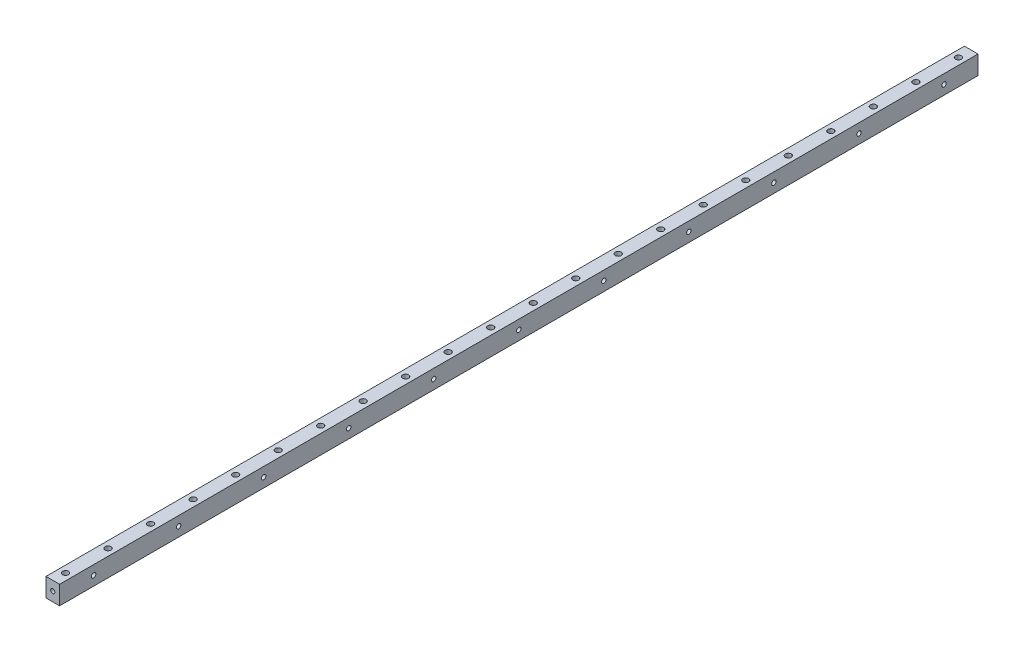
SolidWorks part; units mm, degrees
ref_plane "Front Plane" through (0, 0, 0) normal (0, 0, 1) x (1, 0, 0)
ref_plane "Top Plane" through (0, 0, 0) normal (0, 1, 0) x (1, 0, 0)
ref_plane "Right Plane" through (0, 0, 0) normal (1, 0, 0) x (0, 0, -1)
sketch "Sketch1" plane through (0, 0, 0) normal (0, 0, 1) x (1, 0, 0)
  line L1 (-4, -5.5) -> (4, -5.5)
  line L2 (-4, -5.5) -> (-4, 5.5)
  line L3 (-4, 5.5) -> (4, 5.5)
  line L4 (4, -5.5) -> (4, 5.5)
  line L5 (-4, -5.5) -> (4, 5.5) construction
  line L6 (-4, 5.5) -> (4, -5.5) construction
  point P0 (0, 0)
  dimension "D1" = 8
  dimension "D2" = 11
extrude "Boss-Extrude1" add sketch "Sketch1" along normal blind 540
sketch "Sketch2" plane through (0, 5.5, 0) normal (0, 1, 0) x (1, 0, 0)
  line L0 (4, 0) -> (-4, 0) construction
  circle A0 centre (0, -7.5) radius 1.75
  dimension "D2" = 3.5
  dimension "D1" = 7.5
extrude "Cut-Extrude1" cut sketch "Sketch2" against normal through all
pattern_linear "LPattern1" count 22 spacing 25 along (0, 0, 1) of "Cut-Extrude1"
sketch "Sketch3" plane through (-4, 0, 0) normal (-1, 0, 0) x (0, 0, 1)
  line L0 (0, 0) -> (540, 0) construction
  line L1 (540, 5.5) -> (540, -5.5) construction
  line L2 (0, 5.5) -> (0, -5.5) construction
  circle A0 centre (20, 0) radius 1.3
  dimension "D1" = 2.6
  dimension "D2" = 20
extrude "Cut-Extrude2" cut sketch "Sketch3" against normal through all
pattern_linear "LPattern2" count 11 spacing 50 along (0, 0, 1) of "Cut-Extrude2"
hole_wizard "M3 Tapped Hole1" positions "Sketch6" profile "Sketch8" tap size "M3" standard "ISO"
sketch "Sketch6" plane through (0, 0, 0) normal (0, 0, -1) x (-1, 0, 0)
  line L0 (-4, 5.5) -> (4, -5.5) construction
  point P0 (0, 0)
  point P9 (0, 0)
sketch "Sketch8" plane through (0, 0, 0) normal (1, 0, 0) x (0, 1, 0)
  line L0 (0, 0) -> (0, 8.2511)
  line L1 (0, 8.2511) -> (1.25, 7.5)
  line L2 (1.25, 7.5) -> (1.25, 0)
  line L5 (1.25, 0) -> (0, 0)
  line L10 (0, 8.2511) -> (-1.25, 7.5) construction
  line L11 (0, -6.35) -> (0, 107.95) construction
  dimension "Tap Drill Dia." = 2.5
  dimension "Tap Drill Depth" = 7.5
  dimension "Drill Angle" = 118
cosmetic thread "Hole Thread1"
hole_wizard "M3 Tapped Hole2" positions "Sketch9" profile "Sketch10" tap size "M3" standard "ISO"
sketch "Sketch9" plane through (0, 0, 540) normal (0, 0, 1) x (1, 0, 0)
  line L0 (-4, 5.5) -> (4, -5.5) construction
  point P0 (0, 0)
  point P9 (0, 0)
sketch "Sketch10" plane through (0, 0, 540) normal (1, 0, 0) x (0, -1, 0)
  line L0 (0, 0) -> (0, 8.2511)
  line L1 (0, 8.2511) -> (1.25, 7.5)
  line L2 (1.25, 7.5) -> (1.25, 0)
  line L5 (1.25, 0) -> (0, 0)
  line L10 (0, 8.2511) -> (-1.25, 7.5) construction
  line L11 (0, -6.35) -> (0, 107.95) construction
  dimension "Tap Drill Dia." = 2.5
  dimension "Tap Drill Depth" = 7.5
  dimension "Drill Angle" = 118
cosmetic thread "Hole Thread2"
